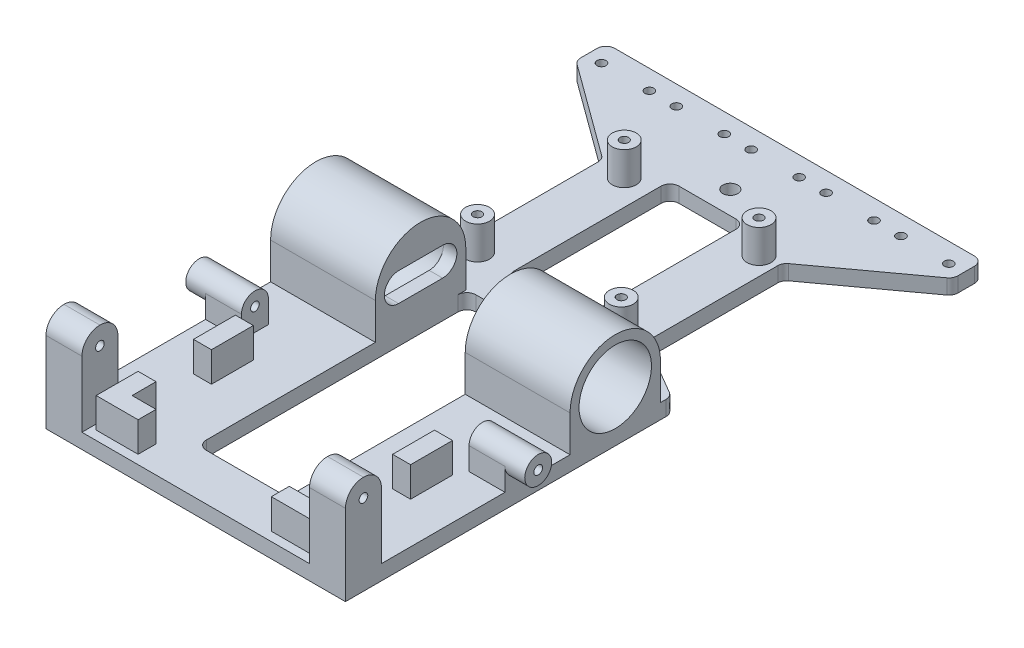
SolidWorks part; units mm, degrees
note: The reader was unsure of these and kept them because the rebuilt part matched: shared geometry of "Sketch4<3>", "Sketch4<4>".
ref_plane "Front Plane" through (0, 0, 0) normal (0, 0, 1) x (1, 0, 0)
ref_plane "Top Plane" through (0, 0, 0) normal (0, 1, 0) x (1, 0, 0)
ref_plane "Right Plane" through (0, 0, 0) normal (1, 0, 0) x (0, 0, -1)
sketch "Sketch1" plane through (0, 0, 0) normal (0, 1, 0) x (1, 0, 0)
  line L0 (0, -55) -> (0, 55) construction
  line L1 (-50, -100) -> (50, -100)
  line L2 (-50, -100) -> (-50, -50)
  line L3 (-50, 100) -> (50, 100)
  line L4 (50, -100) -> (50, -50)
  line L5 (-50, -100) -> (50, 100) construction
  line L6 (-50, 100) -> (50, -100) construction
  line L7 (-63, 100) -> (-63, 90)
  line L8 (-63, 90) -> (-30, 65.8962)
  line L9 (-30, 65.8962) -> (-30, 20.442)
  line L10 (-30, 20.442) -> (-50, 8.7816)
  line L11 (-63, 100) -> (-50, 100)
  line L12 (30, 20.442) -> (50, 8.7816)
  line L13 (30, 65.8962) -> (30, 20.442)
  line L14 (63, 90) -> (30, 65.8962)
  line L15 (63, 100) -> (63, 90)
  line L16 (63, 100) -> (50, 100)
  line L17 (-50, -35) -> (-50, 8.7816)
  line L18 (-15, -84.4613) -> (15, -84.4613)
  line L19 (-15, -84.4613) -> (-15, 5.5387)
  line L20 (-15, 5.5387) -> (15, 5.5387)
  line L21 (15, -84.4613) -> (15, 5.5387)
  line L22 (-15, -84.4613) -> (15, 5.5387) construction
  line L23 (-15, 5.5387) -> (15, -84.4613) construction
  line L24 (-12.5, 15.8812) -> (12.5, 15.8812)
  line L25 (-12.5, 15.8812) -> (-12.5, 70.8812)
  line L26 (-12.5, 70.8812) -> (12.5, 70.8812)
  line L27 (12.5, 15.8812) -> (12.5, 70.8812)
  line L28 (-12.5, 15.8812) -> (12.5, 70.8812) construction
  line L29 (-12.5, 70.8812) -> (12.5, 15.8812) construction
  line L37 (50, -35) -> (50, 8.7816)
  line L38 (-50, -35) -> (-50, -50)
  line L39 (50, -35) -> (50, -50)
  circle A0 centre (0, 78.5204) radius 2.5
  point P0 (0, 0)
  point P18 (0, 43.3812)
  point P19 (0, -39.4613)
  dimension "D10" = 5
  dimension "D1" = 200
  dimension "D2" = 100
  dimension "D3" = 13
  dimension "D4" = 10
  dimension "D5" = 30
  dimension "D6" = 90
  dimension "D7" = 30
  dimension "D8" = 25
  dimension "D9" = 55
extrude "Boss-Extrude1" add sketch "Sketch1" along normal blind 5
fillet "Fillet1" radius 3 18 edges at (15, 2.5, 84.4613) (15, 2.5, -5.5387) (12.5, 2.5, -15.8812) (12.5, 2.5, -70.8812) (63, 2.5, -100) (63, 2.5, -90) (30, 2.5, -65.8962) (30, 2.5, -20.442) (50, 2.5, -8.7816) (-63, 2.5, -100) (-63, 2.5, -90) (-30, 2.5, -65.8962) (-30, 2.5, -20.442) (-50, 2.5, -8.7816) (-12.5, 2.5, -15.8812) (-12.5, 2.5, -70.8812) (-15, 2.5, -5.5387) (-15, 2.5, 84.4613)
sketch "Sketch3" plane through (0, 5, 0) normal (0, 1, 0) x (1, 0, 0)
  line L0 (-50, 7.058) -> (-50, -100) construction
  line L1 (-50, -25) -> (-15, -25)
  line L2 (-50, -25) -> (-50, 5.2)
  line L3 (-50, 5.2) -> (-15, 5.2)
  line L4 (-15, -25) -> (-15, 5.2)
  line L6 (-15, 2.5387) -> (-15, -81.4613) construction
  line L7 (-50, -100) -> (50, -100) construction
  dimension "D1" = 30.2
  dimension "D2" = 75
extrude "Boss-Extrude2" add sketch "Sketch3" along normal blind 27.2
sketch "Sketch4" plane through (-50, 0, 0) normal (-1, 0, 0) x (0, 0, 1)
  line L0 (2.55, 17.1) -> (17.25, 17.1) construction
  line L1 (-5.2, 32.2) -> (-5.2, 5) construction
  line L2 (25, 32.2) -> (25, 5) construction
  line L3 (-5.2, 32.2) -> (25, 32.2) construction
  line L4 (2.55, 21.85) -> (17.25, 21.85)
  line L5 (-5.2, 17.1) -> (-5.2, 32.2)
  line L6 (-5.2, 32.2) -> (9.9, 32.2)
  line L7 (9.9, 32.2) -> (25, 32.2)
  line L8 (25, 32.2) -> (25, 17.1)
  line L9 (2.55, 12.35) -> (17.25, 12.35)
  arc A1 (-5.2, 17.1) -> (25, 17.1) centre (9.9, 17.1) cw
  circle A2 centre (9.9, 17.1) radius 12.1
  arc A3 (2.55, 21.85) -> (2.55, 12.35) centre (2.55, 17.1) ccw
  arc A4 (17.25, 12.35) -> (17.25, 21.85) centre (17.25, 17.1) ccw
  point P15 (9.9, 17.1)
  point P22 (-2.2, 17.1)
  point P23 (22, 17.1)
  line M7 (25, 5) -> (25, 32.2)
  line M8 (25, 32.2) -> (-5.2, 32.2)
  line M9 (-5.2, 32.2) -> (-5.2, 5)
  dimension "D1" = 15.1
  dimension "D2" = 24.2
  dimension "D3" = 24.2
  dimension "D4" = 9.5
extrude "Cut-Extrude1" cut sketch "Sketch4" against normal blind 35 contours A1 M9 M8 | A1 M8 M7
extrude "Cut-Extrude2" cut sketch "Sketch4<3>" against normal blind 30.5
sketch "Sketch4<3>" plane through (-50, 0, 0) normal (-1, 0, 0) x (0, 0, 1) same geometry as "Sketch4"
extrude "Cut-Extrude3" cut sketch "Sketch4<4>" against normal blind 35
sketch "Sketch4<4>" plane through (-50, 0, 0) normal (-1, 0, 0) x (0, 0, 1) same geometry as "Sketch4"
mirror "Mirror9" about plane through (0, 0, 0) normal (1, 0, 0) of "Cut-Extrude3", "Cut-Extrude2", "Cut-Extrude1", "Boss-Extrude2"
sketch "Sketch6" plane through (0, 5, 0) normal (0, 1, 0) x (1, 0, 0)
  line L0 (-50, -25) -> (-50, -100) construction
  line L1 (-50, -46.7315) -> (-38, -46.7315)
  line L2 (-50, -46.7315) -> (-50, -37.7315)
  line L3 (-50, -37.7315) -> (-38, -37.7315)
  line L4 (-38, -46.7315) -> (-38, -37.7315)
  dimension "D1" = 12
  dimension "D2" = 9
extrude "Boss-Extrude3" add sketch "Sketch6" along normal blind 12
fillet "Fillet2" radius 4.5 2 edges at (-44, 17, 37.7315) (-44, 17, 46.7315)
sketch "Sketch9" plane through (-50, 0, 0) normal (-1, 0, 0) x (0, 0, 1)
  circle A0 centre (42.2315, 12.5) radius 4.5
extrude "Boss-Extrude5" add sketch "Sketch9" along normal blind 6.6
sketch "Sketch10" plane through (-56.6, 0, 0) normal (-1, 0, 0) x (0, 0, 1)
  circle A0 centre (42.2315, 12.5) radius 1.45
  dimension "D1" = 2.9
extrude "Cut-Extrude5" cut sketch "Sketch10" against normal blind 18.6
mirror "Mirror11" about plane through (0, 0, 0) normal (1, 0, 0) of "Cut-Extrude5", "Boss-Extrude5", "Fillet2", "Boss-Extrude3"
sketch "Sketch11" plane through (0, 5, 0) normal (0, 1, 0) x (1, 0, 0)
  line L1 (-50, -100) -> (-38, -100)
  line L2 (-50, -100) -> (-50, -88)
  line L3 (-50, -88) -> (-38, -88)
  line L4 (-38, -100) -> (-38, -88)
  dimension "D1" = 12
  dimension "D2" = 12
extrude "Boss-Extrude6" add sketch "Sketch11" along normal blind 28
fillet "Fillet3" radius 6 2 edges at (-44, 33, 88) (-44, 33, 100)
sketch "Sketch12" plane through (-50, 0, 0) normal (-1, 0, 0) x (0, 0, 1)
  circle A0 centre (94, 27) radius 1.45
  point P0 (94, 27)
  dimension "D1" = 2.9
extrude "Cut-Extrude6" cut sketch "Sketch12" against normal blind 12
mirror "Mirror12" about plane through (0, 0, 0) normal (1, 0, 0) of "Cut-Extrude6", "Fillet3", "Boss-Extrude6"
sketch "Sketch13" plane through (0, 5, 0) normal (0, 1, 0) x (1, 0, 0)
  circle A0 centre (-23.995, 18.1083) radius 4
  circle A1 centre (24.005, 18.1083) radius 4
  circle A2 centre (-20.995, 64.1083) radius 4
  circle A3 centre (24.005, 64.1083) radius 4
  circle A4 centre (-23.995, 18.1083) radius 1.45
  circle A5 centre (24.005, 18.1083) radius 1.45
  circle A6 centre (-20.995, 64.1083) radius 1.45
  circle A7 centre (24.005, 64.1083) radius 1.45
  point P0 (-20.995, 64.1083)
  point P1 (24.005, 64.1083)
  point P3 (24.005, 18.1083)
  point P5 (-23.995, 18.1083)
  dimension "D1" = 8
  dimension "D2" = 2.9
extrude "Boss-Extrude7" add sketch "Sketch13" along normal blind 11
sketch "Sketch15" plane through (0, 5, 0) normal (0, 1, 0) x (1, 0, 0)
  line L0 (-30.25, -91) -> (-22.25, -91)
  line L2 (-22.25, -91) -> (-22.25, -97)
  line L3 (-22.25, -97) -> (-36.25, -97)
  line L4 (-36.25, -97) -> (-36.25, -83)
  line L5 (-36.25, -83) -> (-30.25, -83)
  line L7 (-30.25, -83) -> (-30.25, -91)
  line L8 (-38, -100) -> (38, -100) construction
  line L9 (-38, -100) -> (-38, -88) construction
  dimension "D1" = 14
  dimension "D2" = 14
  dimension "D3" = 6
  dimension "D4" = 6
  dimension "D5" = 3
  dimension "D6" = 1.75
extrude "Boss-Extrude8" add sketch "Sketch15" along normal blind 10
mirror "Mirror13" about plane through (0, 0, 0) normal (1, 0, 0) of "Boss-Extrude8"
sketch "Sketch16" plane through (0, 5, 0) normal (0, 1, 0) x (1, 0, 0)
  line L0 (-30.25, -50.5) -> (-30.25, -64.5)
  line L2 (-30.25, -64.5) -> (-36.25, -64.5)
  line L3 (-36.25, -64.5) -> (-36.25, -50.5)
  line L4 (-36.25, -50.5) -> (-30.25, -50.5)
  line L5 (-15, -25) -> (-50, -25) construction
  line L6 (-50, -46.7315) -> (-50, -88) construction
  dimension "D1" = 6
  dimension "D2" = 14
  dimension "D3" = 25.5
  dimension "D4" = 13.75
extrude "Boss-Extrude9" add sketch "Sketch16" along normal blind 10
mirror "Mirror14" about plane through (0, 0, 0) normal (1, 0, 0) of "Boss-Extrude9"
sketch "Sketch17" plane through (0, 5, 0) normal (0, 1, 0) x (1, 0, 0)
  circle A0 centre (-58, 93.5) radius 1.5
  circle A1 centre (-42, 93.5) radius 1.5
  circle A2 centre (-33, 93.5) radius 1.5
  circle A3 centre (-17, 93.5) radius 1.5
  circle A4 centre (-8, 93.5) radius 1.5
  circle A5 centre (8, 93.5) radius 1.5
  circle A6 centre (17, 93.5) radius 1.5
  circle A7 centre (33, 93.5) radius 1.5
  circle A8 centre (42, 93.5) radius 1.5
  circle A9 centre (58, 93.5) radius 1.5
extrude "Cut-Extrude7" cut sketch "Sketch17" against normal up to next
